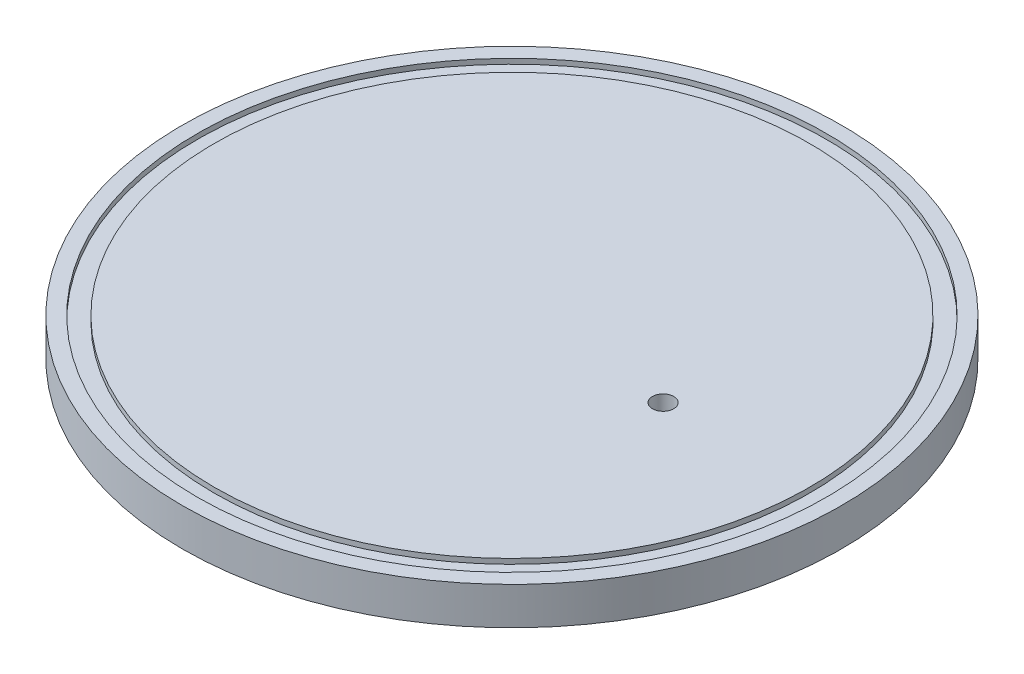
SolidWorks part; units mm, degrees
ref_plane "정면" through (0, 0, 0) normal (0, 0, 1) x (1, 0, 0)
ref_plane "윗면" through (0, 0, 0) normal (0, 1, 0) x (1, 0, 0)
ref_plane "우측면" through (0, 0, 0) normal (1, 0, 0) x (0, 0, -1)
sketch "스케치1" plane through (0, 0, 0) normal (0, 1, 0) x (1, 0, 0)
  circle A1 centre (0, 0) radius 38.5984
  dimension "D1" = 77.1968
extrude "보스-돌출1" add sketch "스케치1" along normal blind 4.4
sketch "스케치2" plane through (0, 4.4, 0) normal (0, 1, 0) x (1, 0, 0)
  circle A0 centre (0, 0) radius 36.8699
  circle A1 centre (0, 0) radius 34.8699
  point P28 (0, 0)
  dimension "D1" = 69.7398
  dimension "D2" = 2
extrude "컷-돌출1" cut sketch "스케치2" against normal blind 0.6
sketch "스케치3" plane through (0, 0, 0) normal (0, -1, 0) x (1, 0, 0)
  line L0 (0, 0) -> (0, 15) construction
  line L1 (0, 0) -> (0, -15) construction
  line L3 (-2.5, -10.5) -> (2.5, -10.5)
  line L4 (-2.5, -10.5) -> (-2.5, -19.5)
  line L5 (-2.5, -19.5) -> (2.5, -19.5)
  line L6 (2.5, -10.5) -> (2.5, -19.5)
  line L7 (-2.5, -10.5) -> (2.5, -19.5) construction
  line L8 (-2.5, -19.5) -> (2.5, -10.5) construction
  line L9 (2.5, 19.5) -> (-2.5, 19.5)
  line L10 (2.5, 19.5) -> (2.5, 10.5)
  line L11 (2.5, 10.5) -> (-2.5, 10.5)
  line L12 (-2.5, 19.5) -> (-2.5, 10.5)
  line L13 (2.5, 19.5) -> (-2.5, 10.5) construction
  line L14 (2.5, 10.5) -> (-2.5, 19.5) construction
  dimension "D1" = 15
  dimension "D2" = 9
  dimension "D3" = 5
extrude "보스-돌출2" add sketch "스케치3" along normal blind 14.5
fillet "필렛2" radius 4.5 4 edges at (0, -14.5, -19.5) (0, -14.5, -10.5) (0, -14.5, 19.5) (0, -14.5, 10.5)
sketch "스케치4" plane through (-2.5, 0, 0) normal (-1, 0, 0) x (0, 0, 1)
  circle A0 centre (-15, -10) radius 1.55
  circle A1 centre (15, -10) radius 1.55
  dimension "D1" = 3.1
extrude "컷-돌출2" cut sketch "스케치4" against normal through all both and the other way through all
sketch "스케치5" plane through (0, 0, 0) normal (0, -1, 0) x (1, 0, 0)
  line L0 (0, 0) -> (17.7, 0) construction
  circle A0 centre (17.7, 0) radius 1.25
  dimension "D2" = 2.5
  dimension "D1" = 17.7
extrude "컷-돌출3" cut sketch "스케치5" against normal through all both
